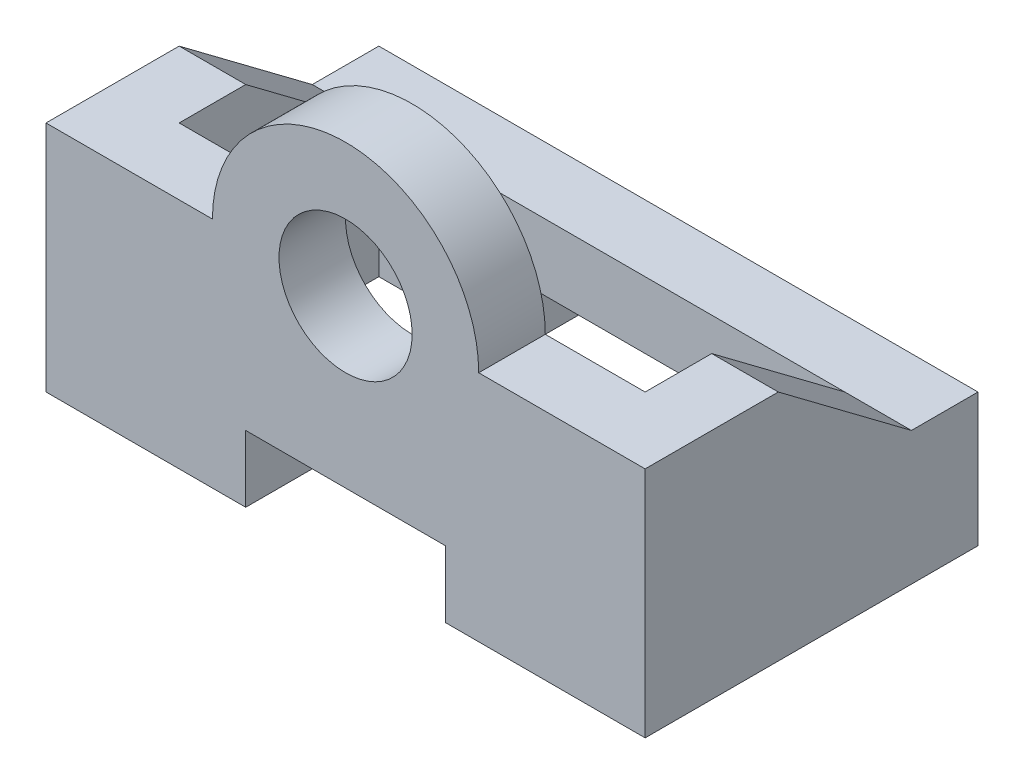
SolidWorks part; units mm, degrees
ref_plane "Front Plane" through (0, 0, 0) normal (0, 0, 1) x (1, 0, 0)
ref_plane "Top Plane" through (0, 0, 0) normal (0, 1, 0) x (1, 0, 0)
ref_plane "Right Plane" through (0, 0, 0) normal (1, 0, 0) x (0, 0, -1)
other "Center of Mass"
sketch "Sketch1" plane through (0, 0, 0) normal (0, 0, 1) x (1, 0, 0)
  line L0 (0, 0) -> (0, 27.5) construction
  line L1 (0, 0) -> (0, -27.5) construction
  line L2 (0, 0) -> (-45, 0) construction
  line L3 (0, 0) -> (45, 0) construction
  line L4 (-45, -27.5) -> (-15, -27.5)
  line L5 (45, -27.5) -> (15, -27.5)
  line L6 (-45, -27.5) -> (-45, -7.5)
  line L7 (45, -27.5) -> (45, -7.5)
  line L8 (-45, -7.5) -> (45, -7.5)
  line L9 (-15, -27.5) -> (-15, -17.5)
  line L10 (15, -27.5) -> (15, -17.5)
  line L11 (-15, -17.5) -> (15, -17.5)
  dimension "D1" = 20
  dimension "D2" = 30
  dimension "D3" = 30
  dimension "D4" = 90
extrude "Boss-Extrude1" add sketch "Sketch1" along normal blind 10
sketch "Sketch2" plane through (0, 0, 0) normal (1, 0, 0) x (0, 0, -1)
  line L0 (0, -27.5) -> (-50, -27.5)
  line L1 (-50, -27.5) -> (-50, 7.5)
  line L2 (-50, 7.5) -> (-30, 7.5)
  line L3 (-30, 7.5) -> (-10, -7.5)
  line L5 (-10, -7.5) -> (-40, -7.5) construction
  line L6 (-50, -7.5) -> (-40, -7.5) construction
  line L11 (0, -27.5) -> (0, -7.5)
  line L12 (0, -7.5) -> (-10, -7.5)
  line L13 (-10, -7.5) -> (-10, -27.5)
  line L14 (-10, -27.5) -> (0, -27.5)
  line L15 (0, -27.5) -> (0, -7.5)
  line L16 (0, -7.5) -> (-10, -7.5)
  dimension "D1" = 30
  dimension "D2" = 10
  dimension "D3" = 20
  dimension "D4" = 35
  dimension "D5" = 50
  dimension "D6" = 0
extrude "Boss-Extrude2" add sketch "Sketch2" along normal mid plane 10 separate body
sketch "Sketch3" plane through (0, 0, 0) normal (0, 0, 1) x (1, 0, 0)
  line L0 (-5, -27.5) -> (-15, -27.5) construction
  line L2 (-15, -27.5) -> (-45, -27.5)
  line L3 (-45, -27.5) -> (-45, 7.5)
  line L4 (-45, 7.5) -> (45, 7.5)
  line L5 (45, 7.5) -> (45, -27.5)
  line L6 (45, -27.5) -> (15, -27.5)
  line L7 (15, -27.5) -> (15, -17.5)
  line L8 (15, -17.5) -> (-15, -17.5)
  line L9 (-15, -17.5) -> (-15, -27.5)
  circle A0 centre (0, 7.5) radius 20
  circle A1 centre (0, 7.5) radius 10
  dimension "D1" = 20
  dimension "D2" = 40
  dimension "D3" = 90
  dimension "D4" = 30
  dimension "D5" = 30
  dimension "D6" = 30
  dimension "D7" = 35
extrude "Boss-Extrude3" add sketch "Sketch3" against normal blind 10 separate body contours A0 L4 L3 L2 L9 L8 L7 L6 L5 | A1 L4 A0 | A1 L4 A0 region at (-30, -26.5343, 0) region at (0, 27.0528, 0) region at (-15, 7.0528, 0)
move or copy body "Body-Move/Copy1" bodies to move or copy 103 copy no translate (0, 0, 50)
move or copy body "Body-Move/Copy2" bodies to move or copy 102 copy no translate (40, 0, 0)
move or copy body "Body-Move/Copy3" bodies to move or copy 105 copy yes number of copies 1 translate (-80, 0, 0)
combine bodies "Combine1" operation type add bodies to combine 105 104 106 101
move or copy body "Body-Move/Copy5" bodies to move or copy 107 copy no translate (0, 0, -25)
